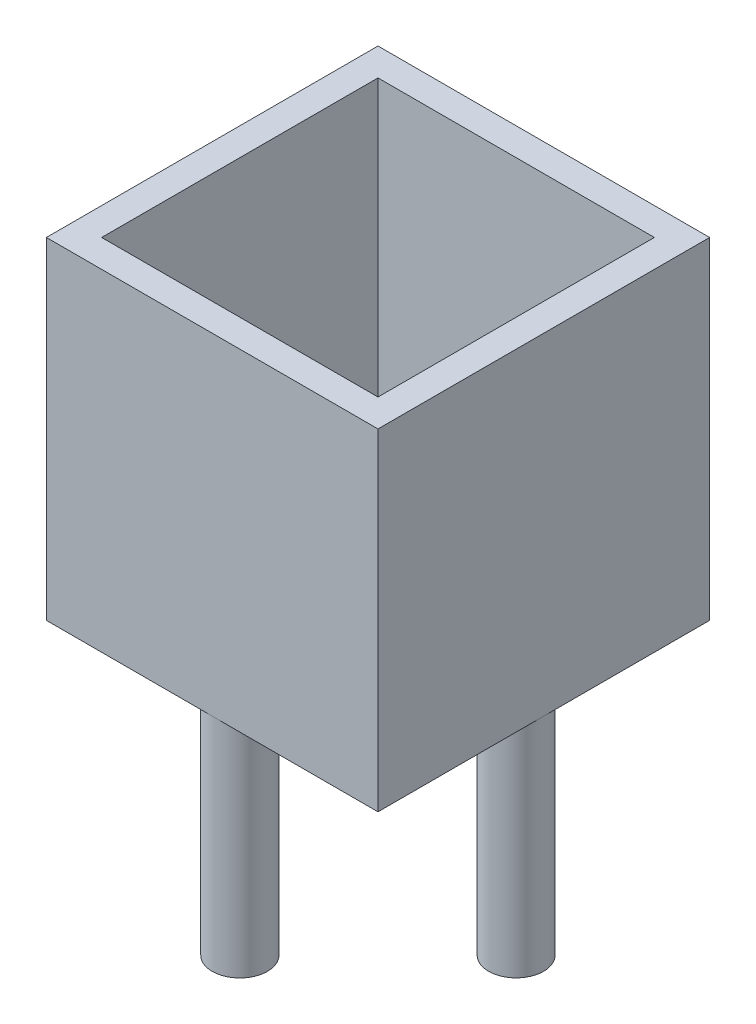
SolidWorks part; units mm, degrees
ref_plane "Front Plane" through (0, 0, 0) normal (0, 0, 1) x (1, 0, 0)
ref_plane "Top Plane" through (0, 0, 0) normal (0, 1, 0) x (1, 0, 0)
ref_plane "Right Plane" through (0, 0, 0) normal (1, 0, 0) x (0, 0, -1)
sketch "Sketch2" plane through (0, 0, 0) normal (0, 1, 0) x (1, 0, 0)
  line L1 (-50, -50) -> (50, -50)
  line L2 (-50, -50) -> (-50, 50)
  line L3 (-50, 50) -> (50, 50)
  line L4 (50, -50) -> (50, 50)
  line L5 (-50, -50) -> (50, 50) construction
  line L6 (-50, 50) -> (50, -50) construction
  line L7 (-60, -60) -> (60, -60)
  line L8 (-60, -60) -> (-60, 60)
  line L9 (-60, 60) -> (60, 60)
  line L10 (60, -60) -> (60, 60)
  line L11 (-60, -60) -> (60, 60) construction
  line L12 (-60, 60) -> (60, -60) construction
  point P0 (0, 0)
  point P6 (0, 0)
extrude "Boss-Extrude1" add sketch "Sketch2" along normal blind 120
sketch "Sketch3" plane through (0, 0, 0) normal (0, -1, 0) x (1, 0, 0)
  line L0 (-60, 60) -> (60, 60)
  line L1 (60, 60) -> (60, -60)
  line L2 (60, -60) -> (-60, -60)
  line L3 (-60, -60) -> (-60, 60)
extrude "Boss-Extrude2" add sketch "Sketch3" against normal blind 10
sketch "Sketch4" plane through (0, 0, 0) normal (0, -1, 0) x (1, 0, 0)
  line L1 (40, 40) -> (-40, 40)
  line L2 (40, 40) -> (40, -40)
  line L3 (40, -40) -> (-40, -40)
  line L4 (-40, 40) -> (-40, -40)
  line L5 (40, 40) -> (-40, -40) construction
  line L6 (40, -40) -> (-40, 40) construction
  point P0 (0, 0)
extrude "Boss-Extrude3" add sketch "Sketch4" along normal blind 30
sketch "Sketch5" plane through (0, -30, 0) normal (0, -1, 0) x (-1, 0, 0)
  circle A0 centre (0, 0) radius 25
extrude "Cut-Extrude2" cut sketch "Sketch5" against normal blind 25
fillet "Fillet1" radius 25 1 edges at (0, -5, -25)
sketch "Sketch7" plane through (0, 0, 0) normal (0, -1, 0) x (1, 0, 0)
  circle A0 centre (0, -50) radius 10
  circle A1 centre (49.9764, 0) radius 9.9764
  circle A2 centre (0, 50) radius 10
  circle A3 centre (-50, 0) radius 10
extrude "Boss-Extrude5" add sketch "Sketch7" along normal blind 80 separate body
sketch "Sketch8" plane through (0, -30, 0) normal (0, -1, 0) x (1, 0, 0)
  line L1 (-40, -40) -> (40, -40)
  line L2 (-40, -40) -> (-40, 40)
  line L3 (-40, 40) -> (40, 40)
  line L4 (40, -40) -> (40, 40)
extrude "Cut-Extrude4" cut sketch "Sketch8" against normal blind 30
